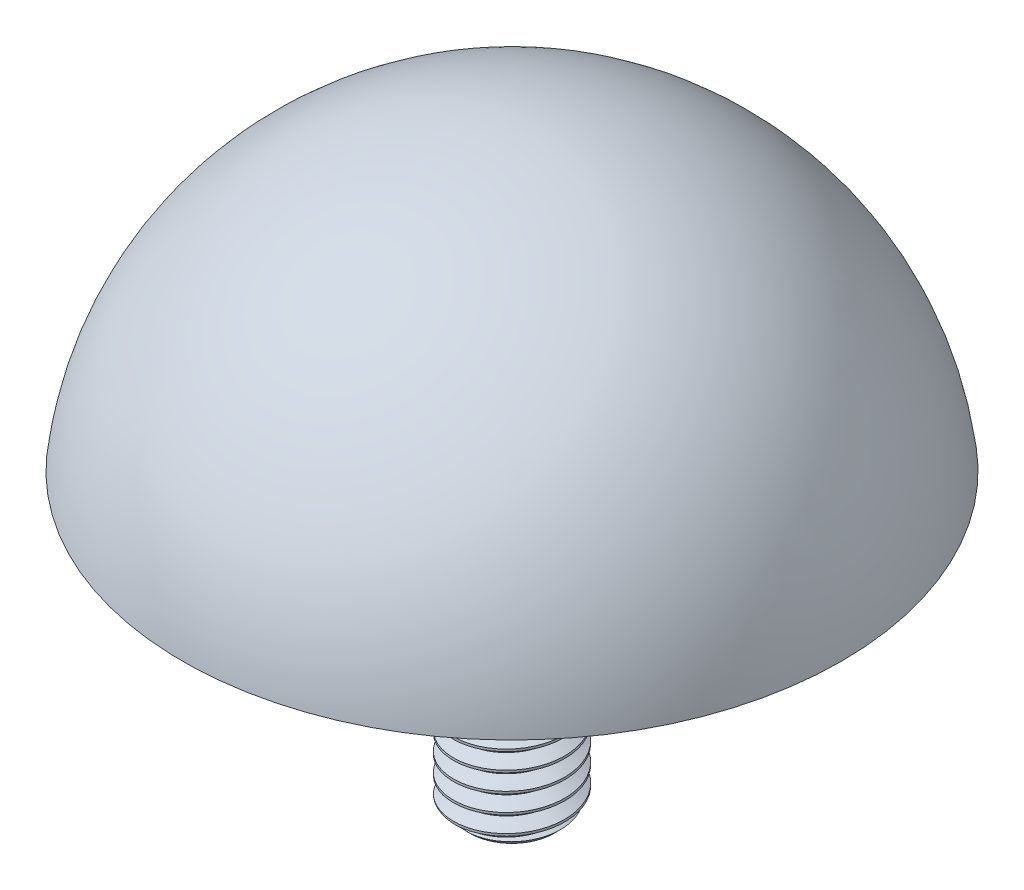
SolidWorks part; units mm, degrees
ref_plane "Front Plane" through (0, 0, 0) normal (0, 0, 1) x (1, 0, 0)
ref_plane "Top Plane" through (0, 0, 0) normal (0, 1, 0) x (1, 0, 0)
ref_plane "Right Plane" through (0, 0, 0) normal (1, 0, 0) x (0, 0, -1)
sketch "Sketch1" plane through (0, 0, 0) normal (0, 0, 1) x (1, 0, 0)
  line L0 (0, 0) -> (0, 12.7) construction
  line L1 (0, 0) -> (0, -12.7) construction
  line L2 (-14.2875, 0) -> (14.2875, 0) construction
  line L3 (2.413, -12.7) -> (-2.413, -12.7) construction
  line L4 (2.4989, -12.6504) -> (1.8115, -13.0473) construction
  line L5 (1.8115, -13.0473) -> (2.4989, -13.4441) construction
  line L6 (2.4989, -13.4441) -> (2.4989, -12.6504) construction
  line L7 (2.413, -12.7) -> (2.413, -13.3945) construction
  line L8 (2.4989, -13.0473) -> (2.413, -13.0473) construction
  line L9 (2.413, -13.0473) -> (1.8974, -13.0473) construction
  line L10 (1.8974, -13.0473) -> (1.8115, -13.0473) construction
  line L11 (1.8974, -12.9977) -> (1.8974, -13.0969)
  line L12 (2.456, -12.6752) -> (2.456, -13.4193)
  line L13 (1.8974, -13.0969) -> (2.456, -13.4193)
  line L14 (1.8974, -12.9977) -> (2.456, -12.6752)
  point P7 (0, 0)
  point P10 (0, -12.7)
  point P22 (2.456, -13.0473)
  point P24 (2.413, -11.1125)
  dimension "OD" = 28.575
  dimension "Height" = 12.7
  dimension "Thread Length" = 12.7
  dimension "Thread Size" = 4.826
  dimension "Pitch" = 0.7937
  dimension "D2" = 0.0992
  dimension "D1" = 1.5875
sketch "Sketch2" plane through (0, 0, 0) normal (0, 0, 1) x (1, 0, 0)
  line L0 (0, -12.7) -> (0, 12.7)
  line L3 (14.2875, 0) -> (2.413, 0)
  line L4 (-14.2875, 0) -> (14.2875, 0) construction
  line L5 (2.413, 0) -> (2.413, -12.7)
  line L6 (2.413, -12.7) -> (0, -12.7)
  arc A2 (14.2875, 0) -> (0, 12.7) centre (0, -1.6867) ccw
revolve "Revolve1" add sketch "Sketch2" angle 360 about L0
sketch "Sketch3" plane through (0, -12.7, 0) normal (0, -1, 0) x (1, 0, 0)
  circle A0 centre (0, 0) radius 2.413 construction
  circle A1 centre (0, 0) radius 2.413
curve "Helix/Spiral1" pitch 0.7937 height 13.4937 radius 2.413 centre (0, -12.7, 0) axis (0, 1, 0) start towards (1, 0, 0) parameters "Pitch"=0.7937
sketch "Sketch4" plane through (0, 0, 0) normal (0, 0, 1) x (1, 0, 0)
  line L4 (1.8974, -12.9977) -> (1.8974, -13.0969) construction
  line L5 (1.8974, -12.9977) -> (2.456, -12.6752) construction
  line L6 (2.456, -12.6752) -> (2.456, -13.4193) construction
  line L7 (1.8974, -13.0969) -> (2.456, -13.4193) construction
  line L8 (1.8974, -12.9977) -> (1.8974, -13.0969)
  line L9 (1.8974, -12.9977) -> (2.456, -12.6752)
  line L10 (2.456, -12.6752) -> (2.456, -13.4193)
  line L11 (1.8974, -13.0969) -> (2.456, -13.4193)
chamfer "Chamfer1" distance 0.5953 angle 45 1 edges at (2.413, -12.7, 0)
sweep "Cut-Sweep1" cut profiles "Sketch4" path "Helix/Spiral1"
equation "\"D3@Helix/Spiral1\"=\"Thread Length@Sketch1\"+\"Pitch@Helix/Spiral1\""
equation "\"D1@Chamfer1\"=\"Pitch@Helix/Spiral1\"*.75"
equation "\"D2@Sketch1\" = \"Pitch@Sketch1\" / 8"
equation "\"D1@Sketch1\"=\"Pitch@Sketch1\"*2"
equation "\"Pitch@Helix/Spiral1\"=\"pitch@sketch1\""
